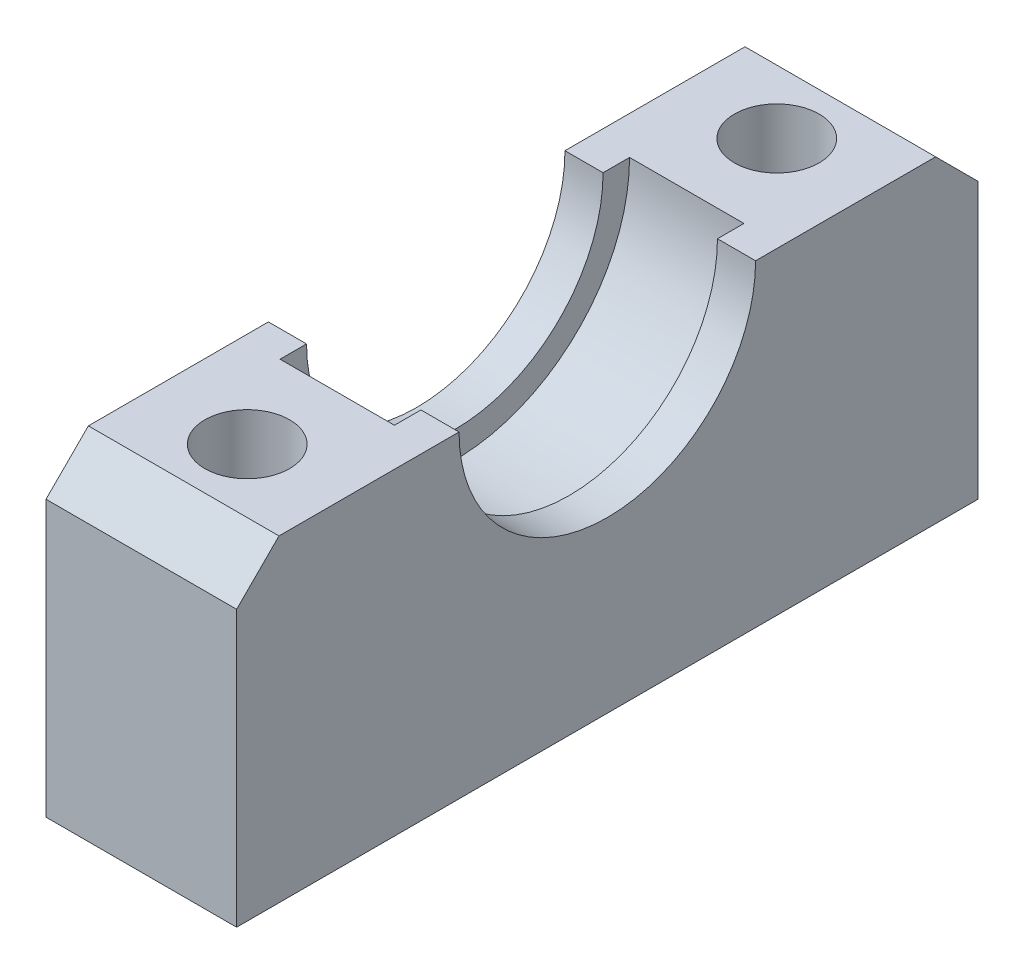
SolidWorks part; units mm, degrees
ref_plane "Front Plane" through (0, 0, 0) normal (0, 0, 1) x (1, 0, 0)
ref_plane "Top Plane" through (0, 0, 0) normal (0, 1, 0) x (1, 0, 0)
ref_plane "Right Plane" through (0, 0, 0) normal (1, 0, 0) x (0, 0, -1)
sketch "Sketch1" plane through (0, 0, 0) normal (1, 0, 0) x (0, 0, -1)
  line L0 (7, 7.5) -> (17.5, 7.5)
  line L1 (-17.5, -7.5) -> (17.5, -7.5)
  line L2 (-17.5, -7.5) -> (-17.5, 7.5)
  line L3 (-17.5, 7.5) -> (-7, 7.5)
  line L4 (17.5, -7.5) -> (17.5, 7.5)
  line L5 (-17.5, -7.5) -> (17.5, 7.5) construction
  line L6 (-17.5, 7.5) -> (17.5, -7.5) construction
  line L7 (0, 0) -> (0, 7.5) construction
  line L8 (0, 7.5) -> (7, 7.5) construction
  arc A0 (-7, 7.5) -> (7, 7.5) centre (0, 7.5) ccw
  point P0 (0, 0)
  dimension "D3" = 14
  dimension "D1" = 15
  dimension "D2" = 35
extrude "Boss-Extrude1" add sketch "Sketch1" along normal blind 4.5 and the other way blind 4.5
sketch "Sketch2" plane through (0, 0, 0) normal (1, 0, 0) x (0, 0, -1)
  circle A0 centre (0, 7.5) radius 8.25
  dimension "D1" = 16.5
extrude "Cut-Extrude1" cut sketch "Sketch2" against normal blind 2.7 and the other way blind 2.7
sketch "Sketch3" plane through (0, 7.5, 0) normal (0, 1, 0) x (1, 0, 0)
  line L0 (-4.5, 17.5) -> (4.5, 17.5) construction
  line L1 (0, 12.5) -> (0, 0) construction
  line L2 (0, 0) -> (0, -12.5) construction
  line L3 (-4.5, -17.5) -> (4.5, -17.5) construction
  circle A0 centre (0, 12.5) radius 2
  circle A1 centre (0, -12.5) radius 2
  dimension "D3" = 4
  dimension "D4" = 4
  dimension "D1" = 5
  dimension "D2" = 5
extrude "Cut-Extrude3" cut sketch "Sketch3" against normal through all
chamfer "Chamfer1" distance 2 angle 45 2 edges at (0, 7.5, -17.5) (0, 7.5, 17.5)
